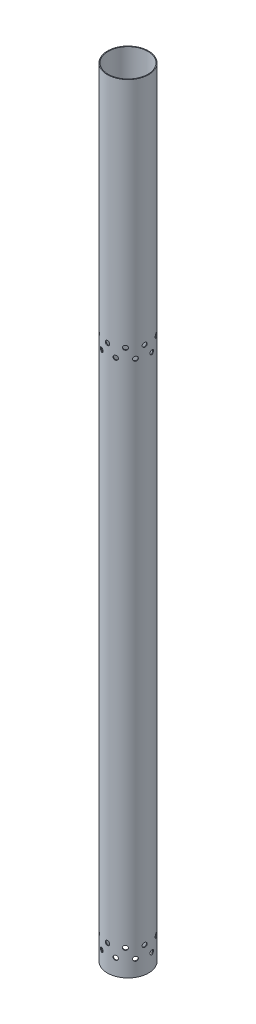
SolidWorks part; units mm, degrees
material "Hexcel AS4C (3000 Filaments)"
ref_plane "Front Plane" through (0, 0, 0) normal (0, 0, 1) x (1, 0, 0)
ref_plane "Top Plane" through (0, 0, 0) normal (0, 1, 0) x (1, 0, 0)
ref_plane "Right Plane" through (0, 0, 0) normal (1, 0, 0) x (0, 0, -1)
sketch "Sketch1" plane through (0, 0, 0) normal (0, 1, 0) x (1, 0, 0)
  circle A0 centre (0, 0) radius 52.7482
  circle A1 centre (0, 0) radius 50.8381
  dimension "D1" = 105.4964
  dimension "D2" = 101.6762
extrude "Boss-Extrude1" add sketch "Sketch1" along normal blind 1993.9
sketch "Sketch4" plane through (0, 0, 0) normal (0, 0, 1) x (1, 0, 0)
  line L1 (-52.7482, 0) -> (52.7482, 0) construction
  circle A0 centre (0, 41.3766) radius 5.5562
  dimension "D1" = 11.1125
  dimension "D2" = 41.3766
extrude "Cut-Extrude2" cut sketch "Sketch4" against normal through all
pattern_circular "CirPattern1" count 9 over 360 about axis through (0, 1993.9, 0) along (0, -1, 0) of "Cut-Extrude2"
ref_plane "Bolt Hole Cut Plane" through (0, 0, 0) normal (-0.342, 0, 0.9397) x (0, -1, 0)
sketch "Sketch7" plane through (0, 0, 0) normal (-0.342, 0, 0.9397) x (0, -1, 0)
  line L0 (-1993.9, 0) -> (0, 0) construction
  line L2 (0, -52.7482) -> (0, 52.7482) construction
  circle A0 centre (-66.7766, 0) radius 5.5562
  dimension "D1" = 11.1125
  dimension "D2" = 66.7766
extrude "Cut-Extrude4" cut sketch "Sketch7" against normal through all
pattern_circular "CirPattern2" count 9 over 360 about axis through (0, 1993.9, 0) along (0, -1, 0) of "Cut-Extrude4"
pattern_linear "LPattern1" count 2 spacing 1331.6966 along (0, 1, 0) of "CirPattern2", "CirPattern1"
